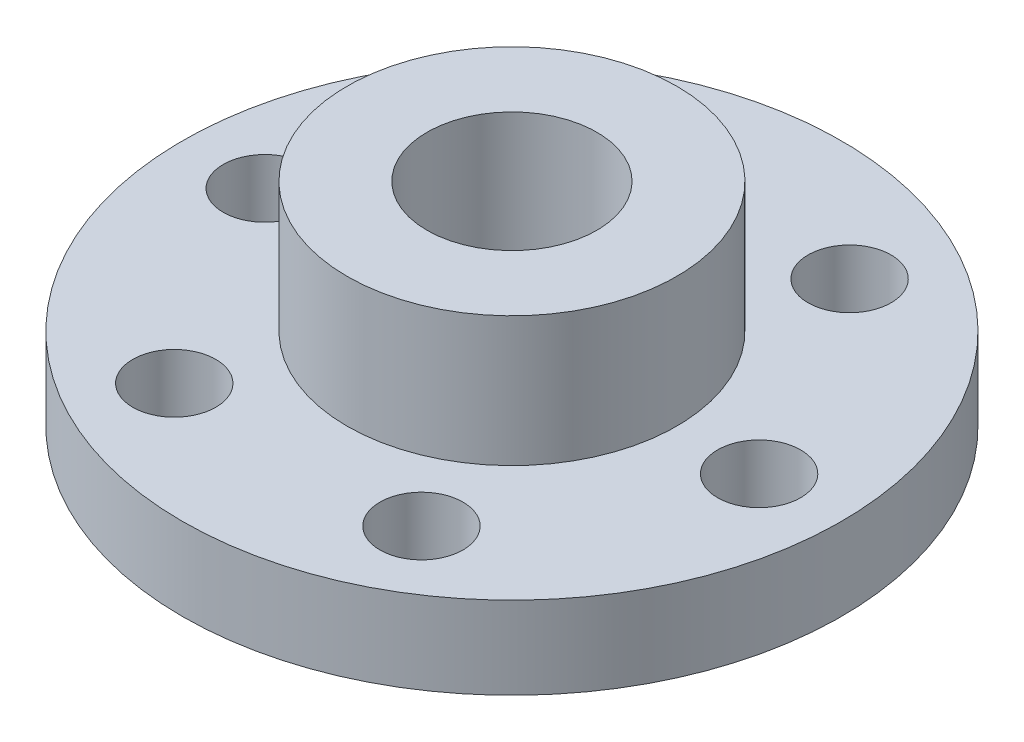
SolidWorks part; units mm, degrees
material "6061-T6 (SS)"
ref_plane "Front Plane" through (0, 0, 0) normal (0, 0, 1) x (1, 0, 0)
ref_plane "Top Plane" through (0, 0, 0) normal (0, 1, 0) x (1, 0, 0)
ref_plane "Right Plane" through (0, 0, 0) normal (1, 0, 0) x (0, 0, -1)
sketch "Sketch1" plane through (0, 0, 0) normal (0, 1, 0) x (1, 0, 0)
  line L0 (0, 0) -> (6.5484, 0) construction
  line L4 (0, 0) -> (-19.05, 0) construction
  circle A0 centre (0, 0) radius 4.826
  circle A1 centre (0, 0) radius 6.5484 construction
  arc A2 (3.9286, 10.8597) -> (3.9286, -10.8597) centre (0, 0) ccw construction
  circle A3 centre (0, 0) radius 25.4
  circle A5 centre (0, 0) radius 11.5484 construction
  circle A6 centre (-19.05, 0) radius 2.9766 construction
  dimension "D1" = 9.652
  dimension "D2" = 13.0969
  dimension "D3" = 23.0969
  dimension "D7" = 5.9531
  dimension "D5" = 50.8
  dimension "D4" = 19.05
extrude "main body" add sketch "Sketch1" along normal blind 6.35
sketch "Sketch2" plane through (0, 6.35, 0) normal (0, 1, 0) x (1, 0, 0)
  circle A0 centre (0, 0) radius 12.7
  circle A2 centre (0, 0) radius 6.5484
  dimension "D1" = 13.0969
  dimension "D2" = 25.4
extrude "tap boss" add sketch "Sketch2" along normal blind 10
hole_wizard "M6 Clearance Hole1" positions "Sketch3" profile "Sketch4" hole size "M6" standard "ANSI Metric" end condition through all
sketch "Sketch3" plane through (0, 6.35, 0) normal (0, 1, 0) x (1, 0, 0)
  point P0 (-19.05, 0)
  point P7 (-9.525, 16.4978)
  point P8 (9.525, 16.4978)
  point P9 (19.05, 0)
  point P10 (9.525, -16.4978)
  point P11 (-9.525, -16.4978)
  point P12 (0, 0)
  dimension "D1" = 6
sketch "Sketch4" plane through (-19.05, 6.35, 0) normal (1, 0, 0) x (0, 0, 1)
  line L0 (0, 0) -> (0, 6.35)
  line L1 (0, 6.35) -> (3.2, 6.35)
  line L2 (3.2, 6.35) -> (3.2, 0)
  line L5 (3.2, 0) -> (0, 0)
  line L11 (0, -6.35) -> (0, 107.95) construction
  dimension "Thru Hole Dia." = 6.4
  dimension "Thru Hole Depth" = 6.35
sketch "Sketch5" plane through (0, 0, 0) normal (0, -1, 0) x (1, 0, 0)
  line L0 (0, 0) -> (-25.4, 0) construction
  line L1 (-25.4, 0) -> (-25.4, 25.4) construction
  line L2 (-25.4, 25.4) -> (0, 25.4) construction
  line L3 (0, 25.4) -> (0, 0) construction
  circle A0 centre (0, 0) radius 25.4 construction
equation "\"z\"= 8\t\t\t\t'number of blades"
equation "\"de\"= 0.43in\t\t\t'entrance eye diameter"
equation "\"de_length\"= 4mm\t\t'entrance eye consistent length"
equation "\"d_exit\"= 0.18in \t\t'throat aka d1"
equation "\"d2\"= 2.1in \t\t\t'outer diameter of the impeller"
equation "\"b2\"= .2in\t\t\t'tip height from disc surface at d2; slightly higher than d_exit"
equation "\"b1\"= \"b2\" + (\"d2\"/2 - \"de\"/2)*tan(\"theta\") \t\t\t'tip height from disc surface at inlet eye"
equation "\"theta\"= 12\t\t\t'angle of blades from inner to outer "
equation "\"ae\"= 3.14*(\"de\"^2)/4\t\t'entrance eye area'"
equation "\"ce\"= 3.14*\"de\"\t\t'entrance eye circumference"
equation "\"av_ratio\"= .325\t\t'ratio of av/ae at N_s of 470, range is .275 to .375, .325 ideal. High ratio means bigger area means smaller blades"
equation "\"av\"= \"ae\"*\"av_ratio\"\t\t'area between just two blades"
equation "\"s_open\"= \"av\"/\"b1\"\t\t'width of open area"
equation "\"s\"=\"ce\" - \"z\"*\"s_open\""
equation "\"min blade thickness\"= .15in"
equation "\"bearing OD\"= 30mm"
equation "\"bearing ID\"= 10mm"
equation "\"bearing depth\"= 9mm"
equation "\"bearing outer race thickness\"= 1mm"
equation "\"bearing inner race thickness\"= 1mm"
equation "\"bearing bore\"= \"bearing depth\" + 1mm"
equation "\"lower seal OD\"= .917in\t\t'this is https://www.mcmaster.com/#9281k121/=174001b"
equation "\"lower seal ID\"= .375in"
equation "\"lower seal depth\"= .625in + .218in"
equation "\"lower seal bore\"= \"lower seal depth\" + 1mm"
equation "\"upper seal OD\"= 1.125in\t'this is https://www.mcmaster.com/#5154t33/=173zuau, needs to be visually inspected before machining!"
equation "\"upper seal ID\"= 0.625in"
equation "\"upper seal depth\"= .25in\t'aka height; these values need to be confirmed by inspection!! We may want to compress the height."
equation "\"upper seal bore\"= \"upper seal depth\" + 1mm"
equation "\"big o-ring thickness\"= .139in"
equation "\"big o-ring OD\"= 2.734in"
equation "\"big o-ring ID\"= 3.012in"
equation "\"big o-ring groove depth\"= \"big o-ring thickness\"*4/5"
equation "\"impeller center height\"= \"impeller base thickness\" + \"b1\"\t'impeller height at de"
equation "\"impeller outer height\"= \"impeller base thickness\" + \"b2\"\t'impeller height at de"
equation "\"impeller upper clearance\"= .5mm"
equation "\"impeller horizontal clearance\"= (\"d2\"*1.15 - \"d2\")/2 \t\t'clearance based on D2-D3 ratio for circular volute, ranges 1.15 to 1.2"
equation "\"impeller bottom clearance\"= .5mm"
equation "\"impeller base thickness\"= 2mm"
equation "\"impeller dowel diameter\"= 2mm"
equation "\"impeller bolt head diameter\"= \"m4 head bore diameter\""
equation "\"impeller bolt head depth\"= 4mm"
equation "\"impeller bolt stop depth\"= 3mm"
equation "\"impeller bolt bore\"= \"m4 clearance\""
equation "\"impeller shaft bore depth\"= 12mm"
equation "\"impeller shaft bore\"= 8mm"
equation "\"impeller boss depth\"= \"impeller shaft bore depth\"+\"impeller bolt stop depth\"+\"impeller bolt head depth\"-\"impeller base thickness\""
equation "\"impeller boss diameter\"= \"upper seal ID\""
equation "\"impeller dowel length\"= 2mm*2 + \"impeller shaft bore\""
equation "\"coupler motor shaft hole ID\"= 8mm"
equation "\"coupler OD\"= 17mm"
equation "\"coupler length\"= 25mm"
equation "\"motor OD\"= 64mm"
equation "\"motor shaft diameter\"= 8mm"
equation "\"motor shaft pride\"= 32mm"
equation "\"motor to bearing plate distance\"= \"motor shaft pride\" + 2mm +\"coupler length\"/2"
equation "\"square plate bolt bore\"= \"m8 clearance\""
equation "\"square plate bolt head diameter\"= 13.5mm"
equation "\"square plate bolt head depth\"= 8mm"
equation "\"square plate bolt pattern diameter\"= 3.5in"
equation "\"motor mount center bore\"= \"coupler OD\"+ 4mm"
equation "\"motor mount post radius\"= ( 3 * \"square plate bolt bore\" ) / 2"
equation "\"motor mount m4 screw hole diameter\"= 4mm"
equation "\"motor mount m4 head diameter\"= 7.25mm"
equation "\"motor mount m4 head depth\"= 4mm"
equation "\"motor mount m4 pattern diamater\"= 30mm"
equation "\"motor mount plate thickness\"= 8mm + \"motor mount m4 head depth\""
equation "\"bearing plate stop ID\"= \"bearing OD\" - 4mm"
equation "\"bearing plate stop depth\"= 3mm"
equation "\"bearing plate thickness\"= \"bearing bore\" + \"bearing plate stop depth\" + \"shaft bearing stop length\""
equation "\"lower seal plate lip depth\"= 2mm"
equation "\"lower seal plate lip ID\"= \"lower seal OD\" - 3mm"
equation "\"lower seal plate thickness\"= \"lower seal plate lip depth\" + \"lower seal bore\""
equation "\"shaft coupler section diameter\"= 8mm"
equation "\"shaft coupler section length\"= \"motor to bearing plate distance\" - \"motor shaft pride\" - 2mm"
equation "\"shaft bearing section diameter\"= \"bearing ID\""
equation "\"shaft bearing section length\"= \"bearing plate stop depth\" + \"bearing depth\""
equation "\"shaft bearing stop diameter\"= \"bearing ID\" + 4mm"
equation "\"shaft bearing stop length\"= 3mm"
equation "\"shaft lower seal section diameter\"= \"lower seal ID\""
equation "\"shaft lower seal section length\"= \"lower seal plate thickness\" + 1mm"
equation "\"shaft impeller section diameter\"= \"impeller shaft bore\""
equation "\"shaft impeller section length\"= \"upper seal plate thickness\" + \"upper seal plate riser\" + \"impeller bottom clearance\" + \"impeller base thickness\" - \"impeller bolt head depth\" - \"impeller bolt stop depth\""
equation "\"upper seal plate thickness\"= \"upper seal plate pressure hole diameter\"+10mm"
equation "\"upper seal plate lip ID\"= \"upper seal OD\" - 3mm"
equation "\"upper seal plate riser\"= 6.59mm \t\t'this number needs to be read from the housing file"
equation "\"upper seal plate pressure hole diameter\"= .125in\t'this is 1/8 drill "
equation "\"upper seal plate pressure tap diameter\"= .328125in \t'this is 21/64 drill for a 1/8 ANPT tap"
equation "\"upper seal plate pressure tap grip\"= 5mm\t\t'this is the area around the tap so it doesn't crack"
equation "\"upper seal plate pressure tap depth\"= 12mm"
equation "\"impeller cavity center height\"= \"impeller bottom clearance\" + \"impeller upper clearance\" + \"impeller center height\""
equation "\"impeller cavity diameter\"= 2 * \"impeller horizontal clearance\" + \"d2\" \t\t\t\t\t\t\t\t\t'called D3 analytically"
equation "\"impeller cavity outer height\"= \"impeller bottom clearance\" + \"impeller upper clearance\" + \"impeller base thickness\" + \"b2\" \t\t'this is height at impeller diameter d2, not at d3"
equation "\"impeller housing thickness\"= \"impeller housing exit threaded diameter\" + 2*\"impeller housing outlet grip\""
equation "\"impeller housing diameter\"= 4.5in"
equation "\"impeller housing bolt count\"= 8"
equation "\"impeller housing bolt diameter\"= \"m6 clearance\""
equation "\"impeller housing bolt pattern diameter\"= 3.5in"
equation "\"impeller housing threaded inlet diameter\"= 0.71875in \t'this is the 23/32 drill size for 1/2 NPT fitting https://www.mcmaster.com/#50715k269/=176pljy"
equation "\"impeller housing threaded inlet depth\"= .6in"
equation "\"impeller housing exit threaded diameter\"= 0.515625in \t\t'this is the 33/64 drill size for 9/16-18 fitting, expecting swagelok SS-8FK0-1-6STH fitting"
equation "\"impeller housing exit threaded depth\"= 10mm"
equation "\"impeller housing diffuser conical angle\"=10"
equation "\"impeller housing diffuser tangent angle\"=5"
equation "\"impeller housing diffuser final diameter\"= .38in\t\t'aka d2'"
equation "\"impeller housing outlet grip\"= 5mm"
equation "\"end mill size\"= 0.375in\t'for 3/8 endmill"
equation "\"m4 clearance\"= 0.171875in \t'this is 11/64 bit for 4.36mm"
equation "\"m4 tap\"= 0.125in\t\t'this is 1/8 bit for 3.17mm"
equation "\"m4 head bore diameter\"= 7.5mm"
equation "\"m4 head bore depth\"= 5mm\t'actual is ~4mm"
equation "\"m6 clearance\"= 0.234375in\t'this is 15/64 bit = 5.95mm, could use 6mm bit, B bit for 6.04mm or 1/4 bit for 6.35mm"
equation "\"m6 tap\"= 5mm\t\t\t'5mm is appropriate, could use 13/64 or #5,6,7"
equation "\"m6 head bore diameter\"= 11mm\t\t"
equation "\"m6 head bore depth\"= 7mm\t'actual is 6mm"
equation "\"m8 clearance\"= 0.3125in\t'this is 5/16in for 7.93mm, could use 8mm, O,P, or 21/64"
equation "\"m8 tap\"= 0.265625in\t\t'this is 17/64 for 6.746875mm"
equation "\"m8 head bore diameter\"= 14mm"
equation "\"m8 head bore depth\"= 9mm\t'actual is 8mm"
equation "\"D1@Sketch1\"=\"impeller housing diffuser final diameter\""
equation "\"D2@Sketch1\"=\"impeller housing exit threaded diameter\""
equation "\"D3@Sketch1\"=\"impeller housing exit threaded diameter\"+\"impeller housing outlet grip\"*2 "
equation "\"D7@Sketch1\"=\"m6 clearance\""
equation "\"D1@Sketch2\"=\"impeller housing exit threaded diameter\""
equation "\"D1@tap boss\"=10mm"
equation "\"diffuser cartridge OD\"=.75in"
equation "\"diffuser flange bolt pattern diameter\"= 1.4in"
equation "\"D4@Sketch1\"=.75in"
